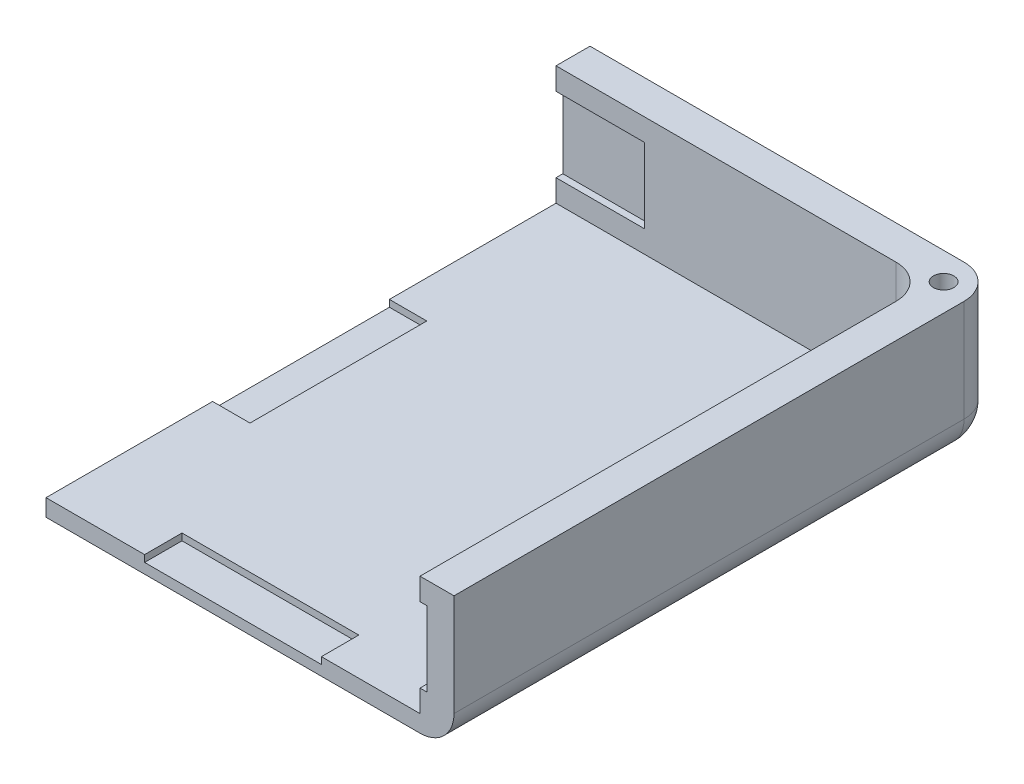
SolidWorks part; units mm, degrees
ref_plane "Plan de face" through (0, 0, 0) normal (0, 0, 1) x (1, 0, 0)
ref_plane "Plan de dessus" through (0, 0, 0) normal (0, 1, 0) x (1, 0, 0)
ref_plane "Plan de droite" through (0, 0, 0) normal (1, 0, 0) x (0, 0, -1)
sketch "Esquisse1" plane through (0, 0, 0) normal (0, 1, 0) x (1, 0, 0)
  line L1 (0, 0) -> (120, 0)
  line L2 (0, 0) -> (0, 160)
  line L3 (0, 160) -> (120, 160)
  line L4 (120, 0) -> (120, 160)
  dimension "D1" = 120
  dimension "D2" = 160
extrude "Boss.-Extru.1" add sketch "Esquisse1" along normal blind 40
fillet "Congé1" radius 10 1 edges at (60, 0, -160)
fillet "Congé2" radius 10 3 edges at (120, 25, -160) (120, 2.9289, -157.0711) (120, 0, -75)
sketch "Esquisse2" plane through (0, 40, 0) normal (0, 1, 0) x (1, 0, 0)
  line L0 (110, 160) -> (0, 160) construction
  line L1 (0, 0) -> (110, 0)
  line L2 (0, 0) -> (0, 150)
  line L3 (0, 150) -> (110, 150)
  line L4 (110, 0) -> (110, 150)
  line L5 (120, 0) -> (120, 150) construction
  dimension "D1" = 10
  dimension "D2" = 10
extrude "Enlèv. mat.-Extru.1" cut sketch "Esquisse2" against normal blind 35
fillet "Congé3" radius 10 1 edges at (110, 22.5, -150)
sketch "Esquisse3" plane through (0, 40, 0) normal (0, 1, 0) x (1, 0, 0)
  line L0 (110, 160) -> (0, 160) construction
  line L1 (120, 0) -> (120, 150) construction
  circle A0 centre (112, 152) radius 3
  dimension "D3" = 6
  dimension "D1" = 8
  dimension "D2" = 8
extrude "Enlèv. mat.-Extru.2" cut sketch "Esquisse3" against normal blind 35
sketch "Esquisse4" plane through (0, 0, 0) normal (0, -1, 0) x (1, 0, 0)
  line L0 (110, -150) -> (110, 0) construction
  line L1 (0, -150) -> (110, -150) construction
  circle A0 centre (90, -130) radius 2.5
  dimension "D3" = 5
  dimension "D1" = 20
  dimension "D2" = 20
extrude "Boss.-Extru.2" add sketch "Esquisse4" along normal blind 2.5
fillet "Congé4" radius 2.5 1 edges at (90, -2.5, -132.5)
sketch "Esquisse5" plane through (0, 5, 0) normal (0, 1, 0) x (1, 0, 0)
  line L0 (0, 150) -> (0, 0) construction
  line L1 (0, 101) -> (11, 101)
  line L2 (0, 101) -> (0, 49)
  line L3 (0, 49) -> (11, 49)
  line L4 (11, 101) -> (11, 49)
  line L5 (0, 0) -> (110, 0) construction
  line L6 (81, 0) -> (29, 0)
  line L7 (81, 0) -> (81, 11)
  line L8 (81, 11) -> (29, 11)
  line L9 (29, 0) -> (29, 11)
  line L10 (100, 150) -> (0, 150) construction
  line L12 (110, 0) -> (110, 140) construction
  point P14 (5.5, 101)
  point P17 (81, 5.5)
  dimension "D1" = 49
  dimension "D2" = 49
  dimension "D3" = 11
  dimension "D4" = 29
  dimension "D5" = 29
  dimension "D6" = 11
extrude "Enlèv. mat.-Extru.3" cut sketch "Esquisse5" against normal blind 2
sketch "Esquisse6" plane through (0, 0, -150) normal (0, 0, 1) x (1, 0, 0)
  line L0 (0, 5) -> (0, 40) construction
  line L1 (0, 33.5) -> (26, 33.5)
  line L2 (0, 33.5) -> (0, 11.5)
  line L3 (0, 11.5) -> (26, 11.5)
  line L4 (26, 33.5) -> (26, 11.5)
  line L5 (100, 40) -> (0, 40) construction
  line L6 (100, 5) -> (0, 5) construction
  dimension "D1" = 6.5
  dimension "D2" = 6.5
  dimension "D3" = 26
extrude "Enlèv. mat.-Extru.4" cut sketch "Esquisse6" against normal blind 2
sketch "Esquisse7" plane through (110, 0, 0) normal (-1, 0, 0) x (0, 0, 1)
  line L0 (0, 5) -> (0, 40) construction
  line L1 (0, 33.5) -> (-26, 33.5)
  line L2 (0, 33.5) -> (0, 11.5)
  line L3 (0, 11.5) -> (-26, 11.5)
  line L4 (-26, 33.5) -> (-26, 11.5)
  line L5 (0, 5) -> (-140, 5) construction
  line L6 (0, 40) -> (-140, 40) construction
  dimension "D1" = 6.5
  dimension "D2" = 6.5
  dimension "D3" = 26
extrude "Enlèv. mat.-Extru.5" cut sketch "Esquisse7" against normal blind 2
